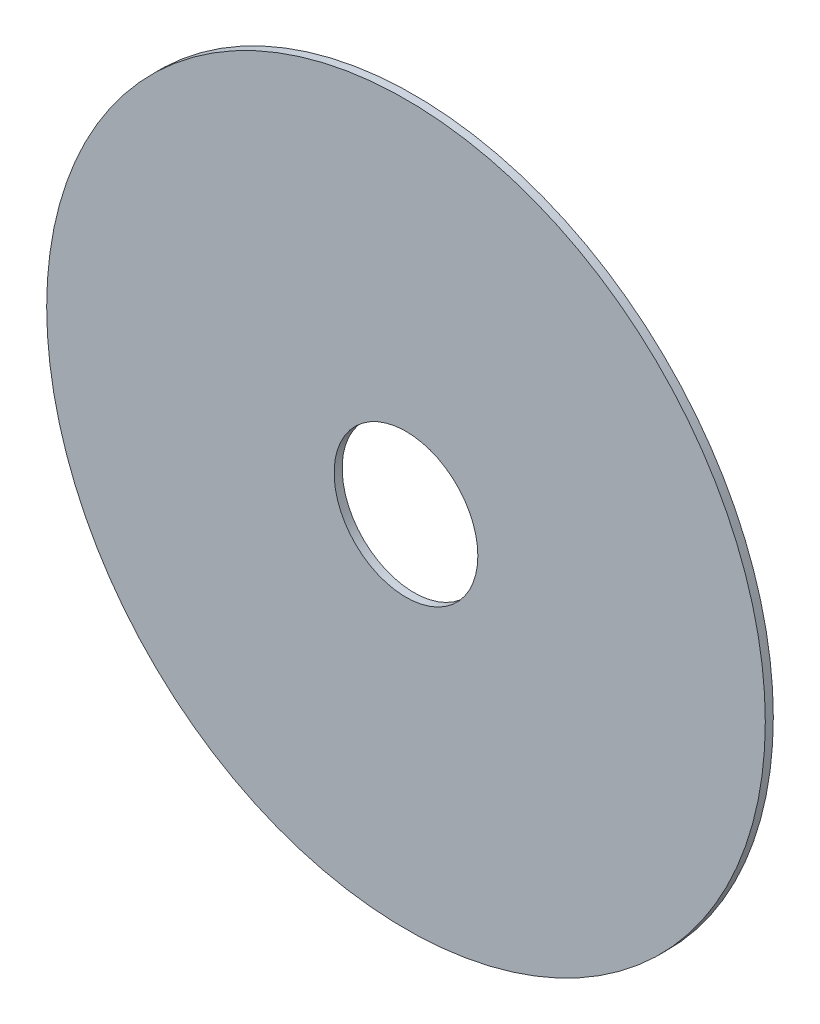
SolidWorks part; units mm, degrees
ref_plane "Front Plane" through (0, 0, 0) normal (0, 0, 1) x (1, 0, 0)
ref_plane "Top Plane" through (0, 0, 0) normal (0, 1, 0) x (1, 0, 0)
ref_plane "Right Plane" through (0, 0, 0) normal (1, 0, 0) x (0, 0, -1)
sketch "Sketch1" plane through (0, 0, 0) normal (0, 0, 1) x (1, 0, 0)
  circle A0 centre (0, 0) radius 11.2
  circle A1 centre (0, 0) radius 56
extrude "Extrude1" add sketch "Sketch1" along normal blind 1.25
